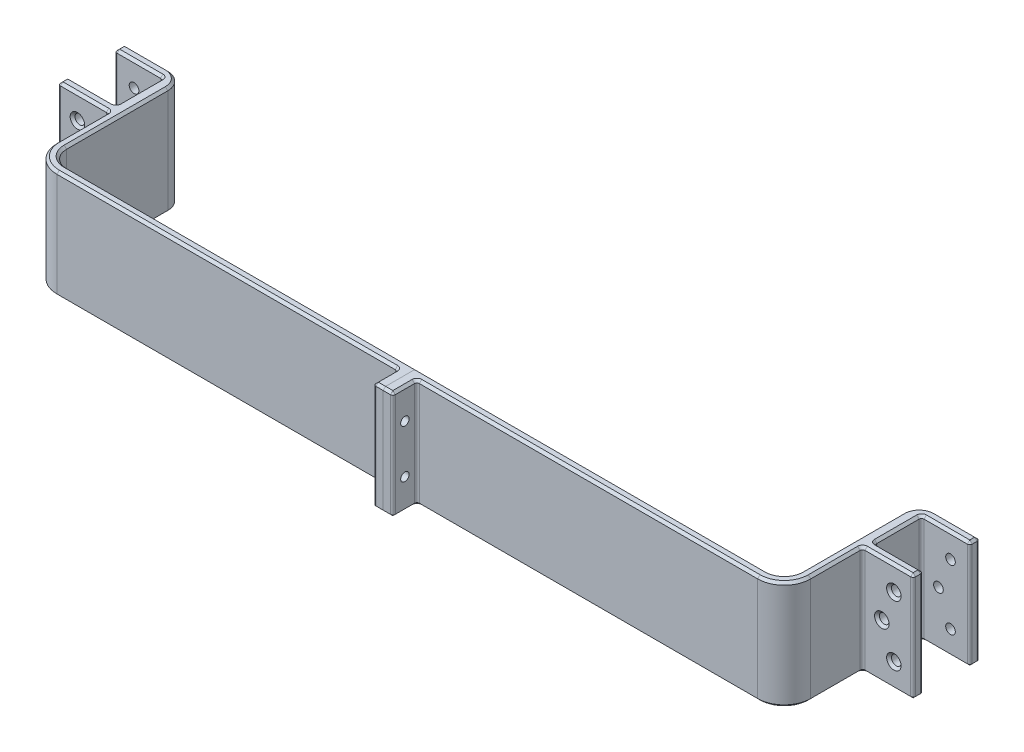
SolidWorks part; units mm, degrees
ref_plane "Front" through (0, 0, 0) normal (0, 0, 1) x (1, 0, 0)
ref_plane "Top" through (0, 0, 0) normal (0, 1, 0) x (1, 0, 0)
ref_plane "Right" through (0, 0, 0) normal (1, 0, 0) x (0, 0, -1)
sketch "Sketch1" plane through (0, 0, 0) normal (0, 1, 0) x (1, 0, 0)
  line L1 (-152.4, 0) -> (-152.4, 56)
  line L2 (-152.4, 56) -> (-177.4, 56)
  line L3 (-177.4, 56) -> (-177.4, 52)
  line L4 (-177.4, 52) -> (-157.4, 52)
  line L5 (-157.4, 52) -> (-157.4, 32.5)
  line L6 (-157.4, 32.5) -> (-177.4, 32.5)
  line L7 (-177.4, 32.5) -> (-177.4, 28.5)
  line L8 (-177.4, 28.5) -> (-156.4, 28.5)
  line L9 (-156.4, 28.5) -> (-156.4, -4)
  line L11 (0, 126.7654) -> (0, -150.0124) construction
  line L22 (0, -14) -> (0, 0)
  line L23 (0, 0) -> (-152.4, 0)
  line L24 (0, -14) -> (-4, -14)
  line L25 (-4, -14) -> (-4, -4)
  line L26 (-4, -4) -> (-156.4, -4)
  point P16 (0, -14)
  point P25 (0, 0)
  dimension "D1" = 304.8
  dimension "D2" = 4
  dimension "D3" = 4
  dimension "D4" = 5
  dimension "D5" = 19.5
  dimension "D6" = 4
  dimension "D7" = 20
  dimension "D8" = 4
  dimension "D9" = 10
  dimension "D10" = 60
extrude "Boss-Extrude1" add sketch "Sketch1" along normal mid plane 45
sketch "Sketch4" plane through (0, 0, -28.5) normal (0, 0, 1) x (1, 0, 0)
  line L0 (0, 0) -> (-119.7332, 0) construction
  line L1 (0, 22.5) -> (0, -22.5) construction
  line L2 (-156.4, 22.5) -> (-156.4, -22.5) construction
  circle A0 centre (-164.4, 0) radius 2
  circle A1 centre (-169.4, 12.5) radius 2
  circle A2 centre (-169.4, -12.5) radius 2
  dimension "D1" = 4
  dimension "D2" = 8
  dimension "D3" = 5
  dimension "D4" = 25
extrude "Cut-Extrude1" cut sketch "Sketch4" against normal through all
sketch "Sketch5" plane through (-4, 0, 0) normal (-1, 0, 0) x (0, 0, 1)
  line L0 (0, 0) -> (26.957, 0) construction
  line L1 (4, 22.5) -> (4, -22.5) construction
  circle A0 centre (9, 10) radius 1.75
  circle A1 centre (9, -10) radius 1.75
  dimension "D1" = 3.5
  dimension "D2" = 20
  dimension "D3" = 5
extrude "Cut-Extrude2" cut sketch "Sketch5" against normal through all
fillet "Fillet1" radius 7 2 edges at (-152.4, 0, -56) (-152.4, 0, 0)
fillet "Fillet3" radius 11 1 edges at (-156.4, 0, 4)
fillet "Fillet2" radius 1 9 edges at (-156.4, 0, -28.5) (-177.4, 0, -32.5) (-157.4, 0, -32.5) (-157.4, 0, -52) (-177.4, 0, -52) (-177.4, 0, -56) (-177.4, 0, -28.5) (-4, 0, 14) (-4, 0, 4)
chamfer "Chamfer1" distance 1 angle 45 50 edges at (-156.4, 22.5, -17.25) (-156.6929, 22.5, -28.2071) (-166.9, 22.5, -28.5) (-177.1071, 22.5, -28.7929) (-177.4, 22.5, -30.5) (-177.1071, 22.5, -32.2071) (-167.4, 22.5, -32.5) (-157.6929, 22.5, -32.7929) (-157.4, 22.5, -42.25) (-157.6929, 22.5, -51.7071) (-167.4, 22.5, -52) (-177.1071, 22.5, -52.2929) (-152.4, 22.5, -28) (-177.4, 22.5, -54) (-154.4503, 22.5, -53.9497) (-177.1071, 22.5, -55.7071) (-167.9, 22.5, -56) (-72.7, 22.5, 0) (-150.3497, 22.5, -2.0503) (-75.2, 22.5, 4) (-1.5, 22.5, 14) (-3.7071, 22.5, 13.7071) (-4, 22.5, 9) (-4.2929, 22.5, 4.2929) (-153.1782, 22.5, 0.7782) (-72.7, -22.5, 0) (-150.3497, -22.5, -2.0503) (-152.4, -22.5, -28) (-154.4503, -22.5, -53.9497) (-167.9, -22.5, -56) (-177.1071, -22.5, -55.7071) (-177.4, -22.5, -54) (-177.1071, -22.5, -52.2929) (-167.4, -22.5, -52) (-157.6929, -22.5, -51.7071) (-157.4, -22.5, -42.25) (-157.6929, -22.5, -32.7929) (-167.4, -22.5, -32.5) (-177.1071, -22.5, -32.2071) (-177.4, -22.5, -30.5) (-177.1071, -22.5, -28.7929) (-166.9, -22.5, -28.5) (-1.5, -22.5, 14) (-156.6929, -22.5, -28.2071) (-3.7071, -22.5, 13.7071) (-156.4, -22.5, -17.25) (-4, -22.5, 9) (-153.1782, -22.5, 0.7782) (-4.2929, -22.5, 4.2929) (-75.2, -22.5, 4)
chamfer "Chamfer2" distance 1 angle 45 6 edges at (-167.4, 12.5, -56) (-162.4, 0, -56) (-167.4, -12.5, -56) (-167.4, -12.5, -28.5) (-162.4, 0, -28.5) (-167.4, 12.5, -28.5)
mirror "Mirror1" about plane through (0, 22.5, 14) normal (-1, 0, 0) of bodies 104 101
